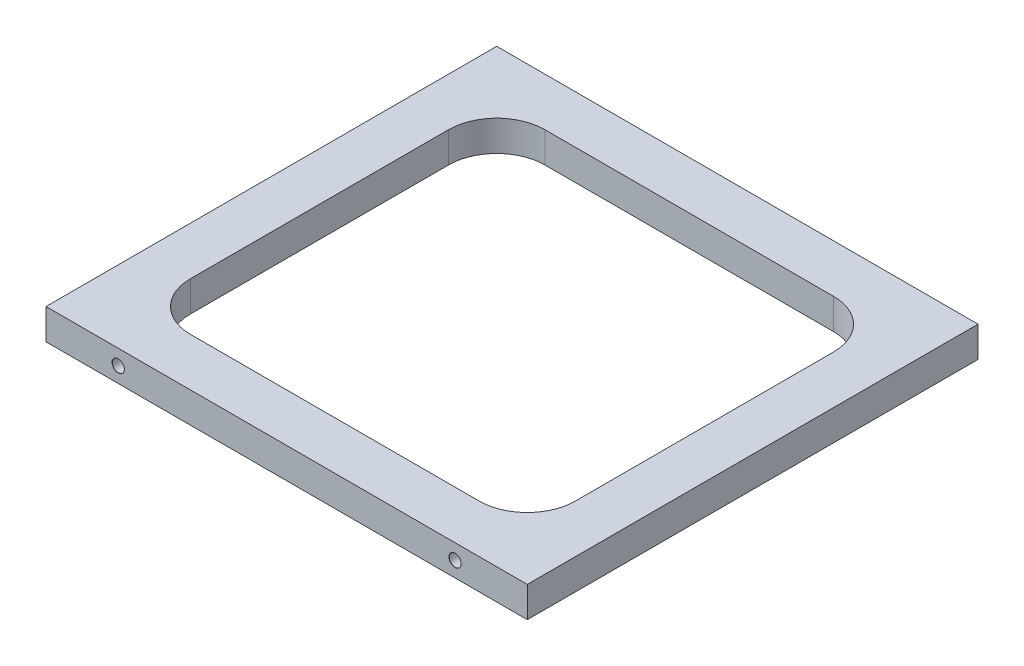
SolidWorks part; units mm, degrees
material "6061 Alloy"
ref_plane "Front Plane" through (0, 0, 0) normal (0, 0, 1) x (1, 0, 0)
ref_plane "Top Plane" through (0, 0, 0) normal (0, 1, 0) x (1, 0, 0)
ref_plane "Right Plane" through (0, 0, 0) normal (1, 0, 0) x (0, 0, -1)
sketch "Sketch1" plane through (0, 0, 0) normal (0, 1, 0) x (1, 0, 0)
  line L1 (-50, -46.825) -> (50, -46.825)
  line L2 (-50, -46.825) -> (-50, 46.825)
  line L3 (-50, 46.825) -> (50, 46.825)
  line L4 (50, -46.825) -> (50, 46.825)
  line L5 (-50, -46.825) -> (50, 46.825) construction
  line L6 (-50, 46.825) -> (50, -46.825) construction
  point P0 (0, 0)
extrude "Boss-Extrude1" add sketch "Sketch1" along normal blind 6.35
sketch "Sketch2" plane through (0, 0, 46.825) normal (0, 0, 1) x (1, 0, 0)
  line L0 (-50, 3.175) -> (-35, 3.175)
  line L1 (-50, 6.35) -> (-50, 0) construction
  line L2 (50, 3.175) -> (35, 3.175)
  line L3 (50, 6.35) -> (50, 0) construction
hole_wizard "Tap Drill for M3x0.5 Tap1" positions "Sketch3" profile "Sketch4" hole size "M3x0.5" standard "ANSI Metric"
sketch "Sketch3" plane through (0, 0, 46.825) normal (0, 0, 1) x (1, 0, 0)
  point P0 (-35, 3.175)
  point P3 (35, 3.175)
sketch "Sketch4" plane through (-35, 3.175, 46.825) normal (1, 0, 0) x (0, -1, 0)
  line L0 (0, 0) -> (0, 10)
  line L1 (0, 10) -> (1.25, 9.2489)
  line L2 (1.25, 9.2489) -> (1.25, 0.025)
  line L3 (1.25, 0.025) -> (1.275, 0)
  line L5 (1.275, 0) -> (0, 0)
  line L6 (-1.25, 0.025) -> (-1.275, 0) construction
  line L10 (0, 10) -> (-1.25, 9.2489) construction
  line L11 (0, -6.35) -> (0, 107.95) construction
  dimension "Hole Dia." = 2.5
  dimension "Hole Depth" = 10
  dimension "Near C'Sink Dia." = 2.55
  dimension "Near C'Sink Angle" = 90
  dimension "Drill Angle" = 118
sketch "Sketch5" plane through (0, 0, -46.825) normal (0, 0, -1) x (-1, 0, 0)
  line L0 (-50, 3.175) -> (-35, 3.175)
  line L1 (50, 3.175) -> (35, 3.175)
hole_wizard "Tap Drill for M3x0.5 Tap2" positions "Sketch6" profile "Sketch7" hole size "M3x0.5" standard "ANSI Metric"
sketch "Sketch6" plane through (0, 0, -46.825) normal (0, 0, -1) x (-1, 0, 0)
  point P0 (-35, 3.175)
  point P3 (35, 3.175)
sketch "Sketch7" plane through (35, 3.175, -46.825) normal (1, 0, 0) x (0, 1, 0)
  line L0 (0, 0) -> (0, 10)
  line L1 (0, 10) -> (1.25, 9.2489)
  line L2 (1.25, 9.2489) -> (1.25, 0.025)
  line L3 (1.25, 0.025) -> (1.275, 0)
  line L5 (1.275, 0) -> (0, 0)
  line L6 (-1.25, 0.025) -> (-1.275, 0) construction
  line L10 (0, 10) -> (-1.25, 9.2489) construction
  line L11 (0, -6.35) -> (0, 107.95) construction
  dimension "Hole Dia." = 2.5
  dimension "Hole Depth" = 10
  dimension "Near C'Sink Dia." = 2.55
  dimension "Near C'Sink Angle" = 90
  dimension "Drill Angle" = 118
sketch "Sketch8" plane through (0, 6.35, 0) normal (0, 1, 0) x (1, 0, 0)
  line L1 (-30, 36.825) -> (30, 36.825)
  line L2 (-40, 26.825) -> (-40, -26.825)
  line L3 (-30, -36.825) -> (30, -36.825)
  line L4 (40, 26.825) -> (40, -26.825)
  line L5 (-40, 36.825) -> (40, -36.825) construction
  line L6 (-40, -36.825) -> (40, 36.825) construction
  arc A0 (-30, -36.825) -> (-40, -26.825) centre (-30, -26.825) cw
  arc A1 (40, -26.825) -> (30, -36.825) centre (30, -26.825) cw
  arc A2 (30, 36.825) -> (40, 26.825) centre (30, 26.825) cw
  arc A3 (-40, 26.825) -> (-30, 36.825) centre (-30, 26.825) cw
  point P0 (0, 0)
  dimension "D1" = 10
extrude "Cut-Extrude1" cut sketch "Sketch8" against normal blind 6.35
